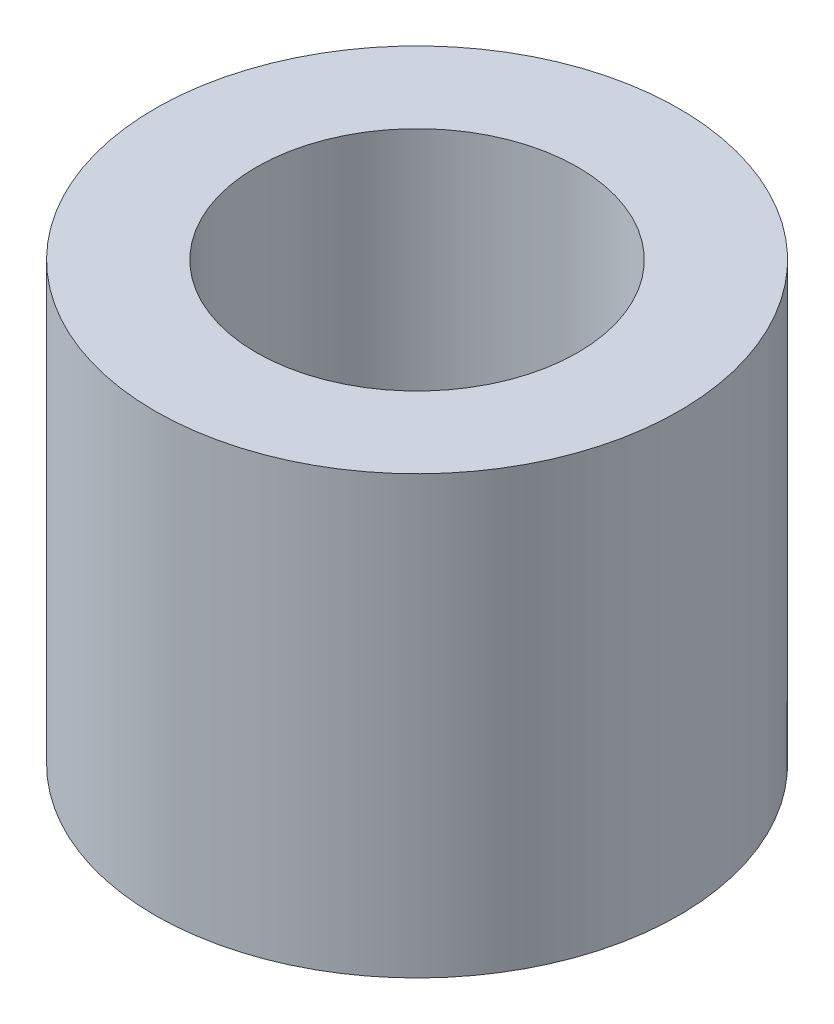
SolidWorks part; units mm, degrees
material "6063-T6"
ref_plane "Front Plane" through (0, 0, 0) normal (0, 0, 1) x (1, 0, 0)
ref_plane "Top Plane" through (0, 0, 0) normal (0, 1, 0) x (1, 0, 0)
ref_plane "Right Plane" through (0, 0, 0) normal (1, 0, 0) x (0, 0, -1)
sketch "Sketch1" plane through (0, 0, 0) normal (0, 1, 0) x (1, 0, 0)
  circle A0 centre (0, 0) radius 15
  circle A1 centre (0, 0) radius 2.5
  point P5 (0, 0)
  dimension "D1" = 30
  dimension "D2" = 5
extrude "Boss-Extrude1" add sketch "Sketch1" along normal blind 25
hole_wizard "G1/4 Tapped Hole1" positions "Sketch2" profile "Sketch4" tap size "G1/4" standard "ISO"
sketch "Sketch2" plane through (0, 25, 0) normal (0, 1, 0) x (1, 0, 0)
  point P0 (0, 0)
sketch "Sketch4" plane through (0, 25, 0) normal (1, 0, 0) x (0, 0, 1)
  line L0 (0, 0) -> (0, 18.5451)
  line L1 (0, 18.5451) -> (5.9, 15)
  line L2 (5.9, 15) -> (5.9, 0)
  line L5 (5.9, 0) -> (0, 0)
  line L10 (0, 18.5451) -> (-5.9, 15) construction
  line L11 (0, -6.35) -> (0, 107.95) construction
  dimension "Tap Drill Dia." = 11.8
  dimension "Tap Drill Depth" = 15
  dimension "Drill Angle" = 118
cosmetic thread "Hole Thread1" parameters "D1"=25, "D2"=13.157
sketch "Sketch14" plane through (0, 0, 0) normal (0, -1, 0) x (1, 0, 0)
  circle A0 centre (0, 0) radius 8.75
  point P2 (2.683, 1.2602)
  point P3 (0, 0)
  circle M3 centre (0, 0) radius 2.5
  dimension "D1" = 17.5
extrude "Cut-Extrude2" cut sketch "Sketch14" against normal blind 10 contours A0 M3 region at (-8.5025, 0, 0)
sketch "Sketch11" plane through (0, 25, 0) normal (0, 1, 0) x (1, 0, 0)
  circle A0 centre (0, 0) radius 9.2
  point P2 (1.3008, 1.3008)
  point P3 (0, 0)
  dimension "D1" = 18.4
extrude "Cut-Extrude3" cut sketch "Sketch11" against normal blind 15 contours A0
